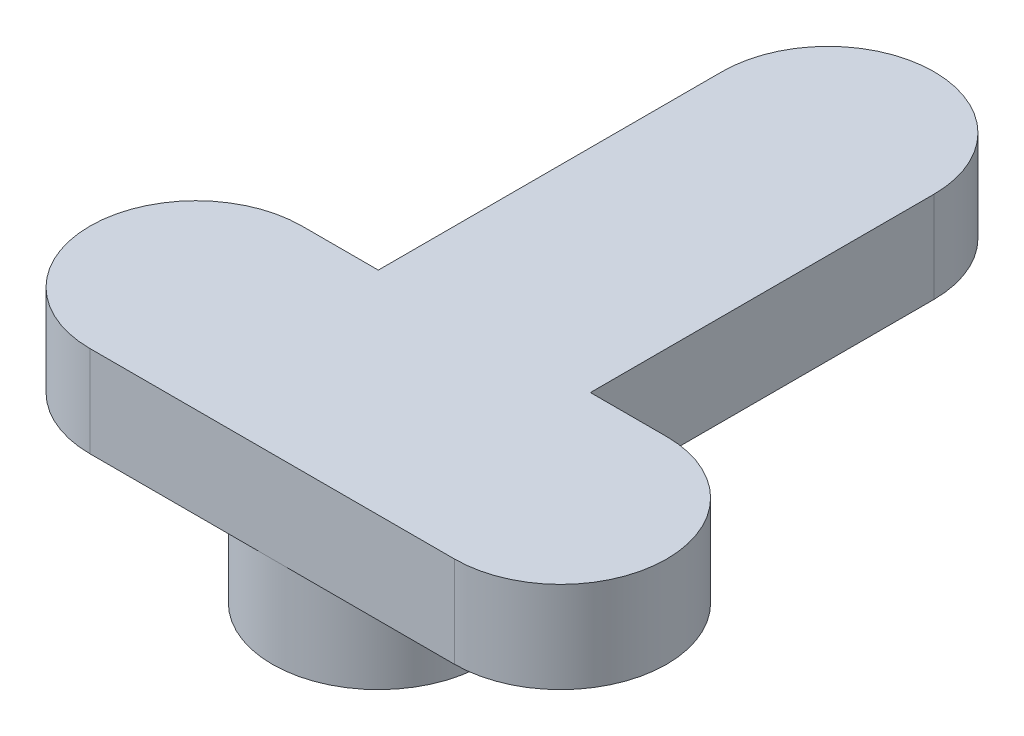
SolidWorks part; units mm, degrees
ref_plane "Front" through (0, 0, 0) normal (0, 0, 1) x (1, 0, 0)
ref_plane "Top" through (0, 0, 0) normal (0, 1, 0) x (1, 0, 0)
ref_plane "Right" through (0, 0, 0) normal (1, 0, 0) x (0, 0, -1)
sketch "Sketch1" plane through (0, 0, 0) normal (0, 1, 0) x (1, 0, 0)
  circle A0 centre (0, 0) radius 2.9547
  dimension "D1" = 5.9094
extrude "Boss-Extrude1" add sketch "Sketch1" along normal blind 2.54
sketch "Sketch2" plane through (0, 2.54, 0) normal (0, 1, 0) x (1, 0, 0)
  line L0 (0, -1.397) -> (0, 1.397) construction
  line L1 (-5.08, 2.9547) -> (5.08, 2.9547)
  line L2 (-5.08, 2.9547) -> (-5.08, -2.9547)
  line L3 (-5.08, -2.9547) -> (5.08, -2.9547)
  line L4 (5.08, 2.9547) -> (5.08, -2.9547)
  line L5 (-5.08, 2.9547) -> (5.08, -2.9547) construction
  line L6 (-5.08, -2.9547) -> (5.08, 2.9547) construction
  line L7 (-1.397, 0) -> (1.397, 0) construction
  line L8 (-2.9547, -12.5296) -> (2.9547, -12.5296)
  line L9 (-2.9547, -12.5296) -> (-2.9547, 12.5296)
  line L10 (-2.9547, 12.5296) -> (2.9547, 12.5296)
  line L11 (2.9547, -12.5296) -> (2.9547, 12.5296)
  line L12 (-2.9547, -12.5296) -> (2.9547, 12.5296) construction
  line L13 (-2.9547, 12.5296) -> (2.9547, -12.5296) construction
  line L14 (-2.9547, -3.6406) -> (2.9547, -3.6406)
  circle A0 centre (0, 0) radius 2.9547 construction
  arc A1 (-5.08, 2.9547) -> (-5.08, -2.9547) centre (-5.08, 0) ccw
  arc A2 (5.08, 2.9547) -> (5.08, -2.9547) centre (5.08, 0) cw
  arc A3 (-2.9547, 12.5296) -> (2.9547, 12.5296) centre (0, 12.5296) cw
  arc A4 (-2.9547, -12.5296) -> (2.9547, -12.5296) centre (0, -12.5296) ccw
  point P0 (0, 0)
  point P12 (0, 0)
  circle M9 centre (0, 0) radius 2.9547
  dimension "D1" = 10.16
extrude "Boss-Extrude2" add sketch "Sketch2" along normal blind 2.54 contours A3 L10 | L1 L11 L10 L9 | L2 A1 | L3 L9 L1 L2 | L11 L1 M9 | M9 | L3 L11 M9 | A2 L4 | L11 L3 L4 L1 | L9 L3 M9 | L9 L1 M9 region at (-4.0173, 2.54, 0) region at (-6.334, 2.54, 0) region at (0, 2.54, -7.7422) region at (-2.2947, 2.54, -2.2947) region at (2.2947, 2.54, -2.2947) region at (0, 2.54, 0) region at (-2.2947, 2.54, 2.2947) region at (0, 2.54, -13.7836) region at (4.0173, 2.54, 0) region at (2.2947, 2.54, 2.2947) region at (6.334, 2.54, 0)
